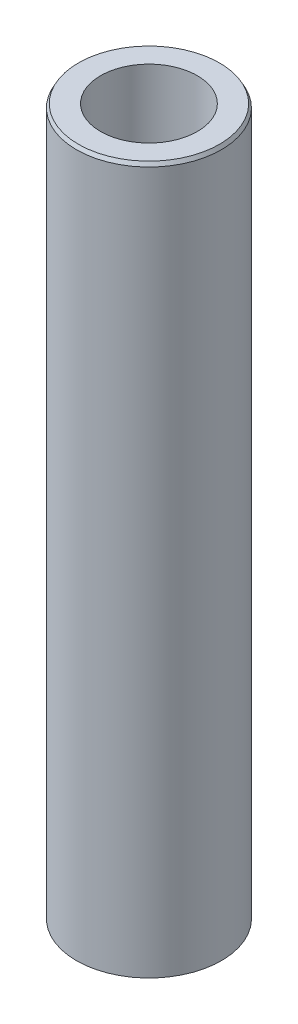
SolidWorks part; units mm, degrees
ref_plane "Front Plane" through (0, 0, 0) normal (0, 0, 1) x (1, 0, 0)
ref_plane "Top Plane" through (0, 0, 0) normal (0, 1, 0) x (1, 0, 0)
ref_plane "Right Plane" through (0, 0, 0) normal (1, 0, 0) x (0, 0, -1)
sketch "Sketch1" plane through (0, 0, 0) normal (0, 1, 0) x (1, 0, 0)
  circle A0 centre (0, 0) radius 57.5
  dimension "SHAFT_OD" = 115
extrude "Boss-Extrude1" add sketch "Sketch1" along normal blind 561.4351
sketch "Sketch2" plane through (0, 0, 0) normal (0, 1, 0) x (1, 0, 0)
  circle A0 centre (0, 0) radius 38.3783
  dimension "BORE_D" = 76.7565
extrude "Cut-Extrude1" cut sketch "Sketch2" along normal through all
chamfer "Chamfer1" distance 2.9395 angle 28.101 2 edges at (0, 561.4351, 57.5) (0, 0, 57.5) first distance on face at (0, 561.4351, 57.5) first distance on face at (0, 0, 38.3783)
